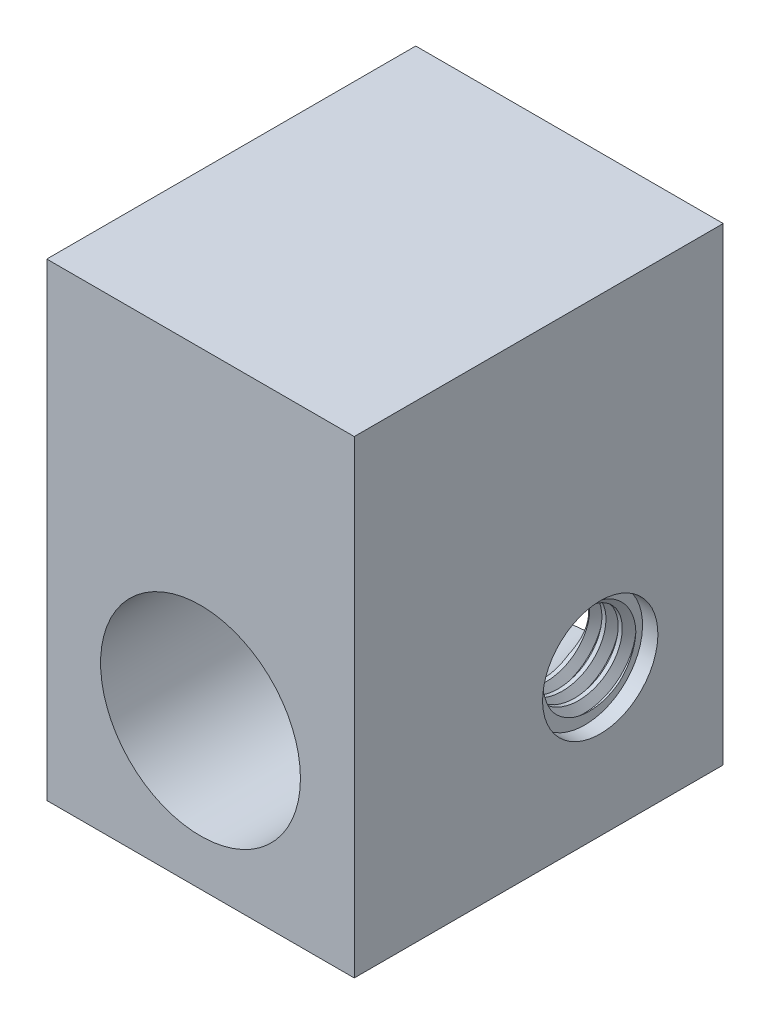
SolidWorks part; units mm, degrees
ref_plane "Front Plane" through (0, 0, 0) normal (0, 0, 1) x (1, 0, 0)
ref_plane "Top Plane" through (0, 0, 0) normal (0, 1, 0) x (1, 0, 0)
ref_plane "Right Plane" through (0, 0, 0) normal (1, 0, 0) x (0, 0, -1)
sketch "Sketch1" plane through (0, 0, 0) normal (0, 0, 1) x (1, 0, 0)
  line L1 (0, 0) -> (-20, 0)
  line L2 (0, 0) -> (0, -30.5)
  line L3 (0, -30.5) -> (-20, -30.5)
  line L4 (-20, 0) -> (-20, -30.5)
  dimension "D1" = 20
  dimension "D2" = 30.5
extrude "Boss-Extrude1" add sketch "Sketch1" along normal blind 24
sketch "Sketch2" plane through (0, 0, 24) normal (0, 0, 1) x (1, 0, 0)
  line L1 (0, 0) -> (-20, 0) construction
  line L2 (-20, -30.5) -> (0, -30.5) construction
  circle A0 centre (-10, -21) radius 6.5
  point P7 (-10, 0)
  dimension "D1" = 9.5
  dimension "D2" = 0
  dimension "D3" = 13
extrude "Cut-Extrude1" cut sketch "Sketch2" against normal blind 40
sketch "Sketch8" plane through (0, 0, 0) normal (0, 0, -1) x (-1, 0, 0)
  line L0 (0, 0) -> (20, 0) construction
  circle A0 centre (10, -10.5) radius 1.75
  point P4 (10, 0)
  dimension "D1" = 0
  dimension "D2" = 3.5
  dimension "D3" = 10.5
extrude "Cut-Extrude5" cut sketch "Sketch8" against normal blind 20
sketch "Sketch13" plane through (0, 0, 0) normal (1, 0, 0) x (0, 0, -1)
  line L0 (-24, -30.5) -> (0, -30.5) construction
  line L1 (0, -30.5) -> (0, 0) construction
  circle A0 centre (-8, -21) radius 2.75
  dimension "D1" = 9.5
  dimension "D2" = 5.5
  dimension "D3" = 8
extrude "Cut-Extrude8" cut sketch "Sketch13" against normal blind 10
thread "Thread3" pitch 1.0583 method cut profile "Thread Profile3" start angle 0, offset 0, length 10, pitch 1.0583, diameter 5.5
ref_plane "Plane3" through (0, -21, 10.75) normal (0, -1, 0) x (0, 0, 1)
sketch "Thread Profile3" plane through (0, -21, 10.75) normal (0, -1, 0) x (0, 0, 1)
  line L0 (0, 0) -> (0, 1.0583) construction
  line L1 (0, 0) -> (0.5728, 0.3307)
  line L2 (0.5728, 0.3307) -> (0.5728, 0.463)
  line L3 (0.5728, 0.463) -> (0, 0.7937)
  line L4 (0.5728, 0.3969) -> (0, 0.3969) construction
  line L11 (0, 0) -> (0, 0.7937)
  point P2 (0, 0)
  dimension "Pitch" = 1.0583
  dimension "Profile_Angle" = 60
  dimension "Profile_Land" = 0.1323
  dimension "Profile_Height" = 0.5728
sketch "Sketch16" plane through (0, 0, 0) normal (1, 0, 0) x (0, 0, -1)
  circle A0 centre (-8, -21) radius 3.75
  dimension "D1" = 7.5
extrude "Cut-Extrude9" cut sketch "Sketch16" against normal blind 1
